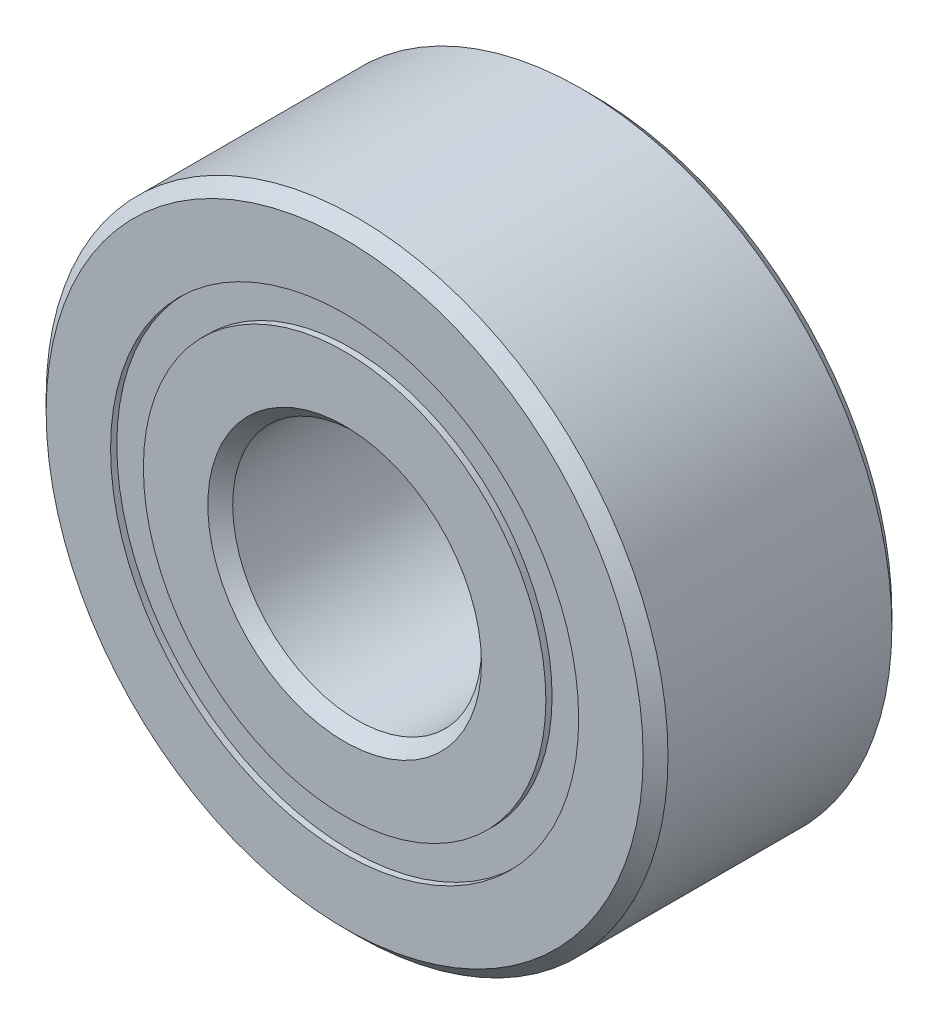
SolidWorks part; units mm, degrees
ref_plane "Front Plane" through (0, 0, 0) normal (0, 0, 1) x (1, 0, 0)
ref_plane "Top Plane" through (0, 0, 0) normal (0, 1, 0) x (1, 0, 0)
ref_plane "Right Plane" through (0, 0, 0) normal (1, 0, 0) x (0, 0, -1)
sketch "Sketch1" plane through (0, 0, 0) normal (1, 0, 0) x (0, 0, -1)
  line L0 (-2, 0) -> (2, 0) construction
  line L1 (0, 5) -> (0, -5) construction
  line L2 (1.8, 5) -> (-1.8, 5)
  line L3 (-1.8, 5) -> (-2, 4.8)
  line L4 (-2, 4.8) -> (-2, 3.7637)
  line L5 (-2, 3.7637) -> (-0.8889, 3.7637)
  line L6 (2, 3.7637) -> (0.8889, 3.7637)
  line L7 (2, 4.8) -> (2, 3.7637)
  line L8 (1.8, 5) -> (2, 4.8)
  line L9 (0, 5) -> (0, 3.5) construction
  line L10 (0, 3.5) -> (0, 2) construction
  arc A0 (-0.8889, 3.7637) -> (0.8889, 3.7637) centre (0, 3.5) cw
  point P14 (0, 2)
  dimension "Width" = 4
  dimension "OD" = 10
  dimension "D1" = 45
  dimension "D2" = 0.2
  dimension "Shaft Dia" = 4
  dimension "D3" = 1.7778
  dimension "D4" = 0.2637
revolve "Revolve1" add sketch "Sketch1" angle 360 about L0
sketch "Sketch3" plane through (0, 0, 0) normal (1, 0, 0) x (0, 0, -1)
  line L0 (-2, 3.2363) -> (-0.8889, 3.2363)
  line L1 (0, 5) -> (0, -5) construction
  line L2 (-2, 4.8) -> (-2, 3.7637) construction
  line L3 (-2, 3.2363) -> (-2, 2.2)
  line L4 (-1.8, 5) -> (-2, 4.8) construction
  line L5 (-2, 2.2) -> (-1.8, 2)
  line L6 (-1.8, 2) -> (1.8, 2)
  line L7 (1.8, 5) -> (1.8, -5) construction
  line L8 (1.8, 2) -> (2, 2.2)
  line L9 (2, -4.8) -> (2, 4.8) construction
  line L10 (2, 2.2) -> (2, 3.2363)
  line L11 (2, 3.2363) -> (0.8889, 3.2363)
  line L13 (1.8, 5) -> (2, 4.8) construction
  arc A0 (0.8889, 3.7637) -> (-0.8889, 3.7637) centre (0, 3.5) ccw construction
  arc A1 (0.8889, 3.2363) -> (-0.8889, 3.2363) centre (0, 3.5) cw
revolve "Revolve3" add sketch "Sketch3" angle 360 about L0
sketch "Sketch4" plane through (0, 0, 0) normal (1, 0, 0) x (0, 0, -1)
  line L0 (-0.9272, 3.5) -> (0.9272, 3.5)
  arc A2 (-0.9272, 3.5) -> (0.9272, 3.5) centre (0, 3.5) cw
  arc A3 (0.8889, 3.7637) -> (-0.8889, 3.7637) centre (0, 3.5) ccw construction
revolve "Revolve4" add sketch "Sketch4" angle 360 about L0
ref_axis "Axis1" through (0, 0, -2) along (0, 0, 1)
pattern_circular "CirPattern1" count 12 every 30 about axis through (0, 0, -2) along (0, 0, 1) of bodies 104
sketch "Sketch5" plane through (0, 0, 0) normal (1, 0, 0) x (0, 0, -1)
  line L0 (-2, 3.7637) -> (-0.8889, 3.7637) construction
  line L1 (-1.9, 3.7637) -> (-0.9272, 3.7637)
  line L2 (-1.9, 3.7637) -> (-1.9, 3.2363)
  line L3 (-1.9, 3.2363) -> (-0.9272, 3.2363)
  line L4 (-0.9272, 3.7637) -> (-0.9272, 3.2363)
  line L5 (-2, 3.2363) -> (-0.8889, 3.2363) construction
  line L6 (2, 3.7637) -> (0.8889, 3.7637) construction
  line L7 (1.9, 3.7637) -> (0.9272, 3.7637)
  line L8 (1.9, 3.7637) -> (1.9, 3.2363)
  line L9 (1.9, 3.2363) -> (0.9272, 3.2363)
  line L10 (0.9272, 3.7637) -> (0.9272, 3.2363)
  line L11 (2, 3.2363) -> (0.8889, 3.2363) construction
  line L12 (-1.8, 5) -> (-2, 4.8) construction
  point P18 (-1.9, 4.9)
revolve "Revolve5" add sketch "Sketch5" angle 360 about L0
sketch "Sketch6" plane through (0, 0, 0) normal (1, 0, 0) x (0, 0, -1)
  line L0 (2, 0) -> (-2, 0) construction
  line L1 (2, 3.7637) -> (0.9, 3.7637)
  line L2 (2, 3.7637) -> (2, 9.5)
  line L3 (2, 9.5) -> (0.9, 9.5)
  line L4 (0.9, 3.7637) -> (0.9, 9.5)
  dimension "Th" = 1.1
  dimension "Flange OD" = 19
revolve "Revolve6" [suppressed] add sketch "Sketch6" angle 360 about L0
equation "\"D2@Sketch1\" = \"Width@Sketch1\"*.05"
equation "\"D3@Sketch1\" = \"Width@Sketch1\"/2.25"
equation "\"D4@Sketch1\" = (((\"OD@Sketch1\"-\"Width@Sketch1\")/2)/3.25)/3.5"
equation "\"D2@CirPattern1\" = 360/\"Balls@CirPattern1\""
